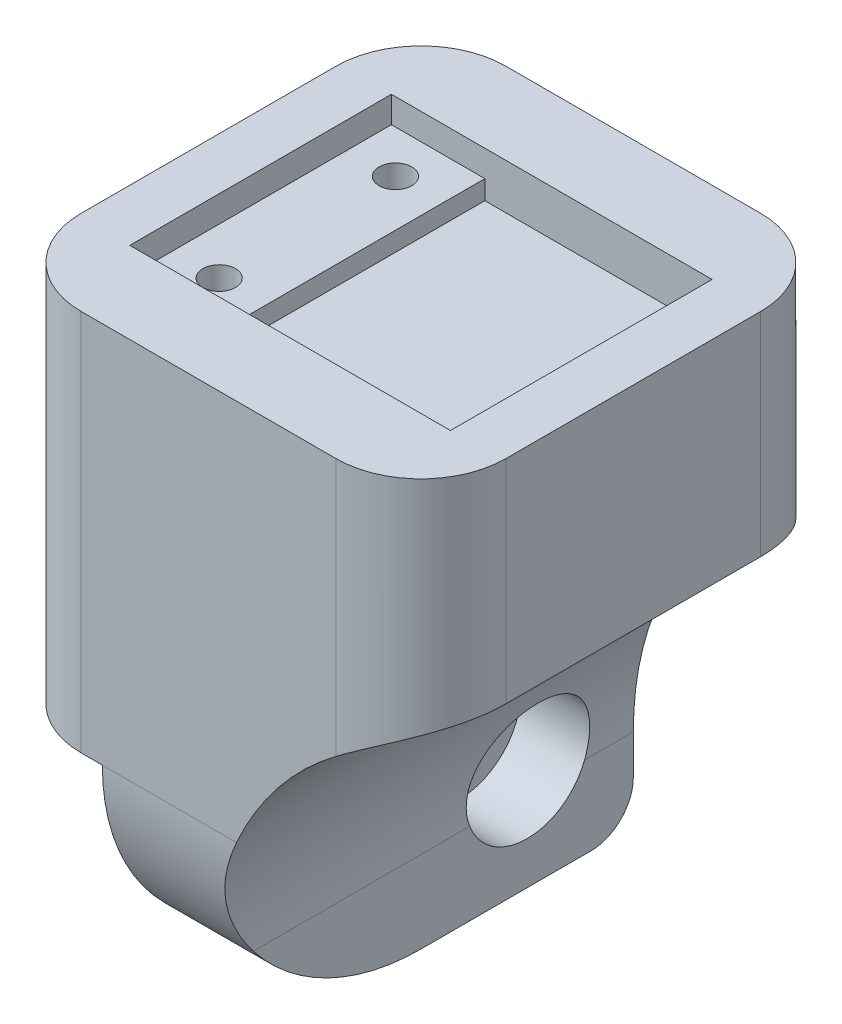
SolidWorks part; units mm, degrees
ref_plane "Front Plane" through (0, 0, 0) normal (0, 0, 1) x (1, 0, 0)
ref_plane "Top Plane" through (0, 0, 0) normal (0, 1, 0) x (1, 0, 0)
ref_plane "Right Plane" through (0, 0, 0) normal (1, 0, 0) x (0, 0, -1)
sketch "Profile" plane through (0, 0, 0) normal (0, 0, 1) x (1, 0, 0)
  line L1 (-6.35, 22.86) -> (6.35, 22.86)
  line L2 (-6.35, 22.86) -> (-6.35, 0)
  line L3 (-6.35, 0) -> (6.35, 0)
  line L4 (6.35, 22.86) -> (6.35, 0)
  line L5 (0, 0) -> (6.35, 0)
  line L6 (0, 0) -> (0, -12.7)
  line L7 (0, -12.7) -> (6.35, -12.7)
  line L8 (6.35, 0) -> (6.35, -12.7)
  dimension "D1" = 22.86
  dimension "D2" = 12.7
  dimension "D3" = 6.35
  dimension "D4" = 12.7
extrude "Boss-Extrude1" add sketch "Profile" along normal mid plane 25.4 contours L4 L1 L2 L3 | L8 L3 L6 L7 region at (0, 11.43, 0) region at (3.175, -6.35, 0)
sketch "ScrewHole" plane through (0, 0, 0) normal (-1, 0, 0) x (0, 0, 1)
  line L0 (-12.7, 0) -> (-12.7, -12.7) construction
  line L2 (12.7, 0) -> (-12.7, 0) construction
  circle A0 centre (-6.35, -6.477) radius 2.159
  point P2 (0, 0)
  point P3 (-6.4165, -6.477)
  dimension "D1" = 4.318
  dimension "D2" = 6.477
  dimension "D3" = 6.35
extrude "Cut-Extrude1" cut sketch "ScrewHole" against normal through all both
sketch "Sketch3" plane through (6.35, 0, 0) normal (1, 0, 0) x (0, 0, -1)
  circle A0 centre (6.35, -6.477) radius 2.159 construction
  circle A1 centre (6.35, -6.477) radius 2.159
  circle A2 centre (6.35, -6.477) radius 3.683
  dimension "D1" = 7.366
extrude "Cut-Extrude2" cut sketch "Sketch3" against normal blind 4.064
sketch "Sketch4" plane through (6.35, 0, 0) normal (1, 0, 0) x (0, 0, -1)
  line L0 (12.7, 22.86) -> (12.7, -12.7) construction
  line L1 (-12.7, 22.86) -> (12.7, 22.86)
  line L2 (-12.7, 22.86) -> (-12.7, 10.16)
  line L3 (-12.7, 10.16) -> (12.7, 10.16)
  line L4 (12.7, 22.86) -> (12.7, 10.16)
  dimension "D1" = 12.7
extrude "Boss-Extrude2" add sketch "Sketch4" along normal blind 12.7
sketch "Sketch6" plane through (0, 22.86, 0) normal (0, 1, 0) x (1, 0, 0)
  line L0 (-6.35, -12.7) -> (-6.35, 12.7) construction
  line L1 (-3.2385, 7.8232) -> (15.9385, 7.8232)
  line L2 (-3.2385, 7.8232) -> (-3.2385, -7.8232)
  line L3 (-3.2385, -7.8232) -> (15.9385, -7.8232)
  line L4 (15.9385, 7.8232) -> (15.9385, -7.8232)
  line L5 (-6.35, -12.7) -> (19.05, -12.7) construction
  point P6 (-6.35, 0)
  point P7 (-3.2385, 0)
  point P10 (6.35, -12.7)
  point P11 (6.35, -7.8232)
  dimension "D1" = 19.177
  dimension "D2" = 15.6464
extrude "Cut-Extrude3" cut sketch "Sketch6" against normal blind 1.5748
sketch "Sketch7" plane through (0, 21.2852, 0) normal (0, 1, 0) x (1, 0, 0)
  line L0 (13.1445, 5.2705) -> (13.1445, -5.2705) construction
  line L1 (15.9385, -7.8232) -> (15.9385, 7.8232) construction
  line L2 (6.35, 7.8232) -> (6.35, -7.8232) construction
  line L3 (15.9385, 7.8232) -> (-3.2385, 7.8232) construction
  line L4 (-3.2385, -7.8232) -> (15.9385, -7.8232) construction
  circle A0 centre (13.1445, 5.2705) radius 0.9779
  circle A1 centre (13.1445, -5.2705) radius 0.9779
  circle A2 centre (-0.4445, -5.2705) radius 0.9779
  circle A3 centre (-0.4445, 5.2705) radius 0.9779
  point P6 (15.9385, 0)
  point P7 (13.1445, 0)
  dimension "D3" = 1.9558
  dimension "D4" = 1.9558
  dimension "D1" = 10.541
  dimension "D2" = 2.794
ref_plane "Plane1" through (6.35, 0, 0) normal (1, 0, 0) x (0, 0, -1)
sketch "Sketch9" plane through (0, 21.2852, 0) normal (0, 1, 0) x (1, 0, 0)
  line L0 (-3.2385, -7.8232) -> (15.9385, -7.8232) construction
  line L1 (2.3495, 7.8232) -> (15.9385, 7.8232)
  line L2 (2.3495, 7.8232) -> (2.3495, -7.8232)
  line L3 (2.3495, -7.8232) -> (15.9385, -7.8232)
  line L4 (15.9385, 7.8232) -> (15.9385, -7.8232)
  line L7 (15.9385, -7.8232) -> (15.9385, 7.8232) construction
  line L8 (-3.2385, 7.8232) -> (-3.2385, -7.8232) construction
  line L9 (15.9385, 7.8232) -> (-3.2385, 7.8232) construction
  dimension "D1" = 5.588
extrude "Cut-Extrude5" cut sketch "Sketch9" against normal blind 1.143
extrude "Cut-Extrude6" cut sketch "Sketch7" against normal blind 12.7 contours A2 | A3
fillet "Fillet1" radius 19.05 1 edges at (6.35, 10.16, 0)
fillet "Fillet2" radius 5.08 4 edges at (-6.35, 11.43, -12.7) (19.05, 16.51, -12.7) (-6.35, 11.43, 12.7) (19.05, 16.51, 12.7)
fillet "Fillet3" radius 12.7 1 edges at (3.175, -12.7, 12.7)
fillet "Fillet4" radius 2.54 1 edges at (3.175, -12.7, -12.7)
